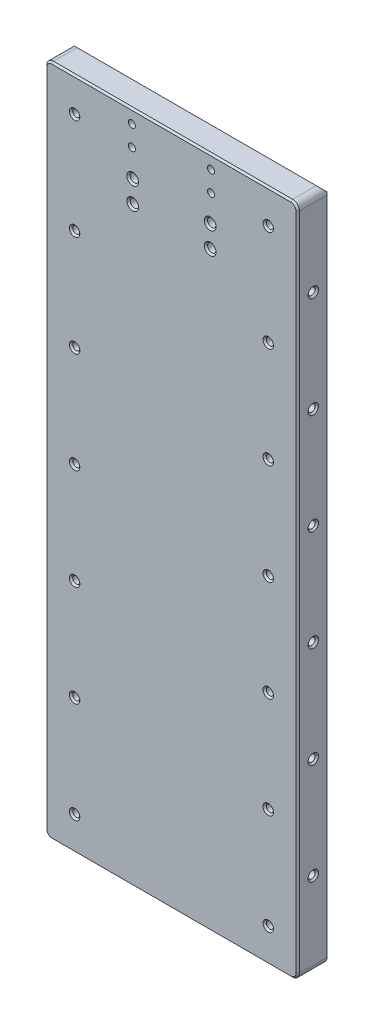
SolidWorks part; units mm, degrees
ref_plane "Front Plane" through (0, 0, 0) normal (0, 0, 1) x (1, 0, 0)
ref_plane "Top Plane" through (0, 0, 0) normal (0, 1, 0) x (1, 0, 0)
ref_plane "Right Plane" through (0, 0, 0) normal (1, 0, 0) x (0, 0, -1)
sketch "Sketch1" plane through (0, 0, 0) normal (0, 0, 1) x (1, 0, 0)
  line L1 (-14, 300) -> (136, 300)
  line L2 (-14, 300) -> (-14, -100)
  line L3 (-14, -100) -> (136, -100)
  line L4 (136, 300) -> (136, -100)
  dimension "D1" = 400
  dimension "D2" = 150
extrude "Boss-Extrude1" add sketch "Sketch1" along normal blind 18.5
sketch "Sketch10" plane through (0, 0, 18.5) normal (0, 0, 1) x (1, 0, 0)
  line L3 (104.1092, 305) -> (136, 300)
  line L4 (136, 300) -> (-14, 300)
  line L6 (17.8908, 305) -> (-14, 300)
  line L8 (61, 305) -> (17.8908, 305)
  line L9 (61, 305) -> (104.1092, 305)
sketch "Sketch2" plane through (0, 0, 0) normal (0, 0, 1) x (1, 0, 0)
  line L0 (61, 272) -> (28, 272)
  line L2 (28, 270) -> (28, 240)
  line L3 (28, 240) -> (94, 240)
  line L4 (94, 240) -> (94, 270)
  line L5 (94, 272) -> (61, 272)
  line L6 (28, 272) -> (28, 270)
  line L7 (94, 272) -> (94, 270)
extrude "Cut-Extrude1" cut sketch "Sketch2" along normal blind 11.5
fillet "Fillet1" radius 4 2 edges at (94, 240, 5.75) (28, 240, 5.75)
sketch "Sketch6" plane through (0, 0, 0) normal (0, 0, -1) x (-1, 0, 0)
  line L4 (-46, 240) -> (-76, 240)
  line L8 (-43, 240) -> (-46, 240)
  line L9 (-76, 240) -> (-79, 240)
  line L24 (-80, 240) -> (-80, 50)
  line L25 (-80, 50) -> (-80, 44)
  line L26 (-42, 50) -> (-42, 240)
  line L27 (-42, 50) -> (-42, 44)
  line L28 (-42, 44) -> (-42, -9)
  line L29 (-42, -25) -> (-42, -9)
  line L30 (-80, -25) -> (-42, -25)
  line L31 (-80, -9) -> (-80, -25)
  line L32 (-80, -9) -> (-80, 44)
  line L33 (-80, 240) -> (-79, 240)
  line L34 (-43, 240) -> (-42, 240)
extrude "Cut-Extrude3" cut sketch "Sketch6" against normal blind 8
sketch "Sketch7" plane through (0, 0, 11.5) normal (0, 0, -1) x (-1, 0, 0)
  circle A4 centre (-84, 264) radius 3.3
  circle A5 centre (-84, 251) radius 3.3
  circle A6 centre (-38, 251) radius 3.3
  circle A7 centre (-38, 264) radius 3.3
hole_wizard "M6x1.0 Tapped Hole1" positions "Sketch8" profile "Sketch9" tap size "M6x1.0" standard "ANSI Metric"
sketch "Sketch8" plane through (0, 0, 11.5) normal (0, 0, -1) x (-1, 0, 0)
  point P12 (-84, 264)
  point P15 (-38, 264)
  point P18 (-38, 251)
  point P21 (-84, 251)
sketch "Sketch9" plane through (84, 264, 11.5) normal (1, 0, 0) x (0, 1, 0)
  line L0 (0, 0) -> (0, 15)
  line L1 (0, 15) -> (2.5, 13.4978)
  line L2 (2.5, 13.4978) -> (2.5, 0)
  line L5 (2.5, 0) -> (0, 0)
  line L10 (0, 15) -> (-2.5, 13.4978) construction
  line L11 (0, -6.35) -> (0, 107.95) construction
  dimension "Tap Drill Dia." = 5
  dimension "Tap Drill Depth" = 15
  dimension "Drill Angle" = 118
cosmetic thread "Hole Thread7"
cosmetic thread "Hole Thread8"
cosmetic thread "Hole Thread9"
cosmetic thread "Hole Thread10"
sketch "Sketch11" plane through (0, 0, 0) normal (0, 0, -1) x (-1, 0, 0)
  line L2 (-61, 262) -> (-79, 262)
  line L3 (-61, 262) -> (-43, 262)
  line L4 (-43, 262) -> (-43, 273)
  line L5 (-47, 277) -> (-75, 277)
  line L6 (-79, 273) -> (-79, 262)
  arc A0 (-43, 273) -> (-47, 277) centre (-47, 273) ccw
  arc A1 (-75, 277) -> (-79, 273) centre (-75, 273) ccw
  dimension "D1" = 4
extrude "Cut-Extrude4" cut sketch "Sketch11" against normal up to surface (11.5 mm away) up to face at (81.5, 264, 11.5)
fillet "Fillet3" radius 4 4 edges at (28, 272, 5.75) (94, 272, 5.75) (43, 272, 5.75) (79, 272, 5.75)
sketch "Sketch12" plane through (0, 0, 0) normal (0, 0, -1) x (-1, 0, 0)
  line L0 (-3.5, -80) -> (-3.5, 280) construction
  line L1 (-118.5, -80) -> (-118.5, 280) construction
  line L2 (-3.5, -80) -> (-3.5, 280)
  line L3 (-118.5, -80) -> (-118.5, 280)
  circle A0 centre (-118.5, 280) radius 2.5
  circle A1 centre (-3.5, 280) radius 2.5
  circle A2 centre (-3.5, 220) radius 2.5
  circle A3 centre (-3.5, 160) radius 2.5
  circle A4 centre (-3.5, 100) radius 2.5
  circle A5 centre (-3.5, 40) radius 2.5
  circle A6 centre (-3.5, -20) radius 2.5
  circle A7 centre (-3.5, -80) radius 2.5
  circle A8 centre (-118.5, 220) radius 2.5
  circle A9 centre (-118.5, 160) radius 2.5
  circle A10 centre (-118.5, 100) radius 2.5
  circle A11 centre (-118.5, 40) radius 2.5
  circle A12 centre (-118.5, -20) radius 2.5
  circle A13 centre (-118.5, -80) radius 2.5
  dimension "D1" = 2
  dimension "D2" = 7
hole_wizard "M5x0.8 Tapped Hole1" positions "Sketch13" profile "Sketch14" tap size "M5x0.8" standard "ANSI Metric" end condition through all
sketch "Sketch13" plane through (0, 0, 0) normal (0, 0, -1) x (-1, 0, 0)
  point P0 (-118.5, 280)
  point P3 (-3.5, 280)
  point P6 (-118.5, 220)
  point P9 (-3.5, 220)
  point P12 (-3.5, 160)
  point P15 (-118.5, 160)
  point P18 (-118.5, 100)
  point P21 (-3.5, 100)
  point P24 (-3.5, 40)
  point P27 (-118.5, 40)
  point P30 (-3.5, -20)
  point P33 (-118.5, -20)
  point P36 (-118.5, -80)
  point P39 (-3.5, -80)
sketch "Sketch14" plane through (118.5, 280, 0) normal (1, 0, 0) x (0, 1, 0)
  line L0 (0, 0) -> (0, 18.5)
  line L1 (0, 18.5) -> (2.1, 18.5)
  line L2 (2.1, 18.5) -> (2.1, 0)
  line L5 (2.1, 0) -> (0, 0)
  line L11 (0, -6.35) -> (0, 107.95) construction
  dimension "Thru Tap Drill Dia." = 4.2
  dimension "Thru Tap Drill Depth" = 18.5
cosmetic thread "Hole Thread11"
cosmetic thread "Hole Thread12"
cosmetic thread "Hole Thread13"
cosmetic thread "Hole Thread14"
cosmetic thread "Hole Thread15"
cosmetic thread "Hole Thread16"
cosmetic thread "Hole Thread17"
cosmetic thread "Hole Thread18"
cosmetic thread "Hole Thread19"
cosmetic thread "Hole Thread20"
cosmetic thread "Hole Thread21"
cosmetic thread "Hole Thread22"
cosmetic thread "Hole Thread23"
cosmetic thread "Hole Thread24"
fillet "Fillet5" radius 4 4 edges at (-14, -100, 9.25) (136, -100, 9.25) (136, 300, 9.25) (-14, 300, 9.25)
chamfer "Chamfer2" distance 1 angle 45 26 edges at (-12.8284, 298.8284, 18.5) (61, 300, 18.5) (134.8284, 298.8284, 18.5) (136, 100, 18.5) (134.8284, -98.8284, 18.5) (61, -100, 18.5) (-12.8284, -98.8284, 18.5) (-14, 100, 18.5) (86.5, 251, 18.5) (40.5, 251, 18.5) (40.5, 264, 18.5) (86.5, 264, 18.5) (1.4, -80, 18.5) (116.4, -80, 18.5) (116.4, -20, 18.5) (1.4, -20, 18.5) (116.4, 40, 18.5) (1.4, 40, 18.5) (1.4, 100, 18.5) (116.4, 100, 18.5) (116.4, 160, 18.5) (1.4, 160, 18.5) (1.4, 220, 18.5) (116.4, 220, 18.5) (1.4, 280, 18.5) (116.4, 280, 18.5)
fillet "Fillet6" radius 4 4 edges at (42, 240, 4) (80, 240, 4) (42, -25, 4) (80, -25, 4)
chamfer "Chamfer3" distance 3 angle 45 22 edges at (41.8199, 272.6834, 0) (44.7639, 276.3166, 0) (35.7919, 272, 0) (61, 277, 0) (29.1716, 270.8284, 0) (77.2361, 276.3166, 0) (28, 256, 0) (80.1801, 272.6834, 0) (29.1716, 241.1716, 0) (86.2081, 272, 0) (35, 240, 0) (92.8284, 270.8284, 0) (40.8284, 238.8284, 0) (94, 256, 0) (42, 107.5, 0) (92.8284, 241.1716, 0) (43.1716, -23.8284, 0) (87, 240, 0) (61, -25, 0) (81.1716, 238.8284, 0) (78.8284, -23.8284, 0) (80, 107.5, 0)
chamfer "Chamfer4" distance 3.5 angle 45 1 edges at (61, 300, 0) tangent propagation no
chamfer "Chamfer5" distance 1 angle 45 7 edges at (135.9921, 296.2505, 0) (136, 100, 0) (134.8284, -98.8284, 0) (61, -100, 0) (-13.9921, 296.2505, 0) (-12.8284, -98.8284, 0) (-14, 100, 0)
sketch "Sketch15" plane through (-14, 0, 0) normal (-1, 0, 0) x (0, 0, 1)
  circle A0 centre (9.25, 250) radius 2.1
  circle A1 centre (9.25, 190) radius 2.1
  circle A2 centre (9.25, 130) radius 2.1
  circle A3 centre (9.25, 70) radius 2.1
  circle A4 centre (9.25, 10) radius 2.1
  circle A5 centre (9.25, -50) radius 2.1
sketch "Sketch16" plane through (136, 0, 0) normal (1, 0, 0) x (0, 0, -1)
  circle A0 centre (-9.25, 250) radius 2.1
  circle A1 centre (-9.25, 190) radius 2.1
  circle A2 centre (-9.25, 130) radius 2.1
  circle A3 centre (-9.25, 70) radius 2.1
  circle A4 centre (-9.25, 10) radius 2.1
  circle A5 centre (-9.25, -50) radius 2.1
extrude "Cut-Extrude5" cut sketch "Sketch15" against normal blind 17
extrude "Cut-Extrude6" cut sketch "Sketch16" against normal blind 17
chamfer "Chamfer6" distance 1 angle 45 26 edges at (-14, -52.1, 9.25) (-14, 7.9, 9.25) (-14, 67.9, 9.25) (-14, 127.9, 9.25) (-14, 187.9, 9.25) (-14, 247.9, 9.25) (136, 252.1, 9.25) (136, 192.1, 9.25) (136, 132.1, 9.25) (136, 72.1, 9.25) (136, 12.1, 9.25) (136, -47.9, 9.25) (1.4, -80, 0) (116.4, -80, 0) (1.4, -20, 0) (116.4, -20, 0) (1.4, 40, 0) (116.4, 40, 0) (1.4, 100, 0) (116.4, 100, 0) (116.4, 160, 0) (116.4, 220, 0) (1.4, 220, 0) (1.4, 280, 0) (116.4, 280, 0) (1.4, 160, 0)
sketch "Sketch17" plane through (0, 0, 0) normal (0, 0, -1) x (-1, 0, 0)
  circle A0 centre (-84.5, 292) radius 2.1
  circle A1 centre (-84.5, 280) radius 2.1
  circle A2 centre (-37.5, 292) radius 2.1
  circle A3 centre (-37.5, 280) radius 2.1
extrude "Cut-Extrude7" cut sketch "Sketch17" against normal through all
